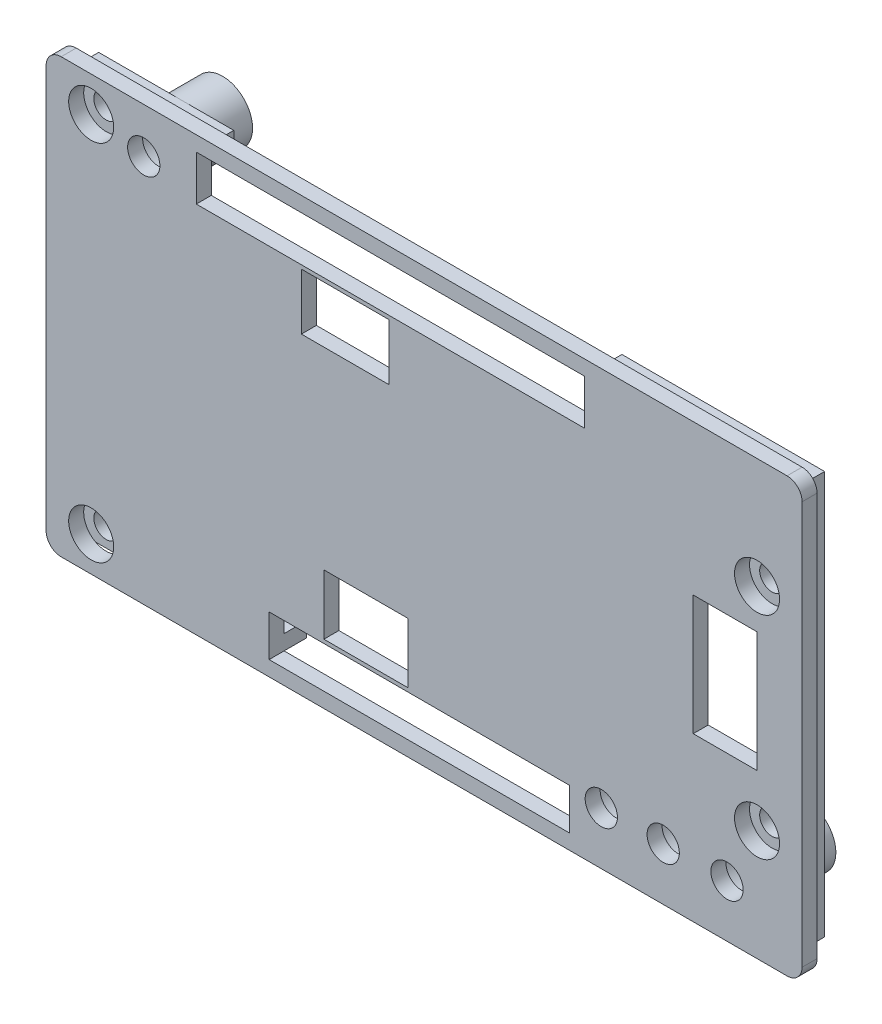
SolidWorks part; units mm, degrees
ref_plane "Front Plane" through (0, 0, 0) normal (0, 0, 1) x (1, 0, 0)
ref_plane "Top Plane" through (0, 0, 0) normal (0, 1, 0) x (1, 0, 0)
ref_plane "Right Plane" through (0, 0, 0) normal (1, 0, 0) x (0, 0, -1)
sketch "Sketch1" plane through (0, 0, 0) normal (0, 0, 1) x (1, 0, 0)
  line L1 (-48.35, 26.85) -> (48.35, 26.85)
  line L2 (-48.35, 26.85) -> (-48.35, -26.85)
  line L3 (-48.35, -26.85) -> (48.35, -26.85)
  line L4 (48.35, 26.85) -> (48.35, -26.85)
  line L5 (-46.35, 24.85) -> (46.35, 24.85)
  line L6 (-46.35, 24.85) -> (-46.35, -24.85)
  line L7 (-46.35, -24.85) -> (46.35, -24.85)
  line L8 (46.35, 24.85) -> (46.35, -24.85)
  line L9 (-50.35, 28.85) -> (50.35, 28.85)
  line L10 (-50.35, 28.85) -> (-50.35, -28.85)
  line L11 (-50.35, -28.85) -> (50.35, -28.85)
  line L12 (50.35, 28.85) -> (50.35, -28.85)
  dimension "D1" = 96.7
  dimension "D2" = 53.7
  dimension "D3" = 26.85
  dimension "D4" = 48.35
  dimension "D5" = 2
  dimension "D6" = 2
  dimension "D7" = 2
  dimension "D8" = 2
  dimension "D9" = 2
  dimension "D10" = 2
  dimension "D11" = 2
  dimension "D12" = 2
extrude "Boss-Extrude1" add sketch "Sketch1" along normal blind 2 contours L8 L5 L6 L7 | L4 L1 L2 L3 L5 L8 L7 L6 | L12 L9 L10 L11 L1 L4 L3 L2 region at (0, 25.7439, 0) region at (0, 0, 0) region at (0, 27.6894, 0)
fillet "Fillet1" radius 2 4 edges at (-50.35, -28.85, 1) (-50.35, 28.85, 1) (50.35, -28.85, 1) (50.35, 28.85, 1)
extrude "Boss-Extrude2" add sketch "Sketch1<3>" against normal blind 3 contours L4 L1 L2 L3 L5 L8 L7 L6 region at (0, 25.7439, 0)
sketch "Sketch1<3>" plane through (0, 0, 0) normal (0, 0, 1) x (1, 0, 0) same geometry as "Sketch1"
sketch "Sketch2" plane through (-48.35, 0, 0) normal (-1, 0, 0) x (0, 0, 1)
  line L4 (-3, -10.005) -> (-3, -20.478)
  line L7 (-3, 26.85) -> (-3, -26.85) construction
  arc A0 (-3, -20.478) -> (-3, -10.005) centre (-5.0085, -15.2415) ccw
  dimension "D4" = 0
extrude "Cut-Extrude2" cut sketch "Sketch2" against normal blind 17 and the other way blind 3
sketch "Sketch4" plane through (0, 0, 0) normal (0, 0, -1) x (-1, 0, 0)
  line L0 (48.35, 26.85) -> (-48.35, 26.85) construction
  line L1 (-48.35, 26.85) -> (-48.35, -26.85) construction
  line L2 (48.35, -26.85) -> (-48.35, -26.85) construction
  line L3 (-48.35, 26.85) -> (-48.35, -26.85) construction
  line L4 (48.35, -17.7654) -> (48.35, -26.85) construction
  line L5 (48.35, -26.85) -> (-48.35, -26.85) construction
  line L7 (48.35, 26.85) -> (48.35, -12.7176) construction
  line L8 (48.35, 26.85) -> (-48.35, 26.85) construction
  circle A2 centre (-44.35, -14.1) radius 1.65
  circle A3 centre (-44.35, 14.1) radius 1.65
  circle A4 centre (44.35, 24.2) radius 1.65
  circle A7 centre (44.35, -24.2) radius 1.65
  dimension "D2" = 4
  dimension "D4" = 4
  dimension "D5" = 3.3
  dimension "D6" = 3.3
  dimension "D10" = 2.65
  dimension "D11" = 3.3
  dimension "D14" = 2.65
  dimension "D15" = 3.3
  dimension "D1" = 12.75
  dimension "D3" = 12.75
  dimension "D9" = 4
  dimension "D13" = 4
sketch "Sketch5" plane through (0, 0, 2) normal (0, 0, 1) x (1, 0, 0)
  line L0 (-48.35, -28.85) -> (48.35, -28.85) construction
  line L1 (-48.35, 26.85) -> (48.35, 26.85)
  line L2 (-48.35, 26.85) -> (-48.35, -26.85)
  line L3 (-48.35, -26.85) -> (48.35, -26.85)
  line L4 (48.35, 26.85) -> (48.35, -26.85)
  line L5 (-50.35, 26.85) -> (-50.35, -26.85) construction
  line L6 (-48.35, 28.85) -> (48.35, 28.85) construction
  line L7 (50.35, 26.85) -> (50.35, -26.85) construction
  line L9 (-20.65, -21.35) -> (19.35, -21.35)
  line L10 (-20.65, -21.35) -> (-20.65, -26.85)
  line L11 (-20.65, -26.85) -> (19.35, -26.85)
  line L12 (19.35, -21.35) -> (19.35, -26.85)
  line L13 (-30.35, 26.85) -> (21.35, 26.85)
  line L14 (-30.35, 26.85) -> (-30.35, 20.85)
  line L15 (-30.35, 20.85) -> (21.35, 20.85)
  line L16 (21.35, 26.85) -> (21.35, 20.85)
  line L17 (35.85, 8.85) -> (44.35, 8.85)
  line L18 (35.85, 8.85) -> (35.85, -7.15)
  line L19 (35.85, -7.15) -> (44.35, -7.15)
  line L20 (44.35, 8.85) -> (44.35, -7.15)
  line L21 (-13.35, -12.85) -> (-2.15, -12.85)
  line L22 (-13.35, -12.85) -> (-13.35, -20.85)
  line L23 (-13.35, -20.85) -> (-2.15, -20.85)
  line L24 (-2.15, -12.85) -> (-2.15, -20.85)
  line L25 (-16.35, 20.35) -> (-4.65, 20.35)
  line L26 (-16.35, 20.35) -> (-16.35, 12.85)
  line L27 (-16.35, 12.85) -> (-4.65, 12.85)
  line L28 (-4.65, 20.35) -> (-4.65, 12.85)
  dimension "D1" = 2
  dimension "D2" = 2
  dimension "D3" = 2
  dimension "D4" = 2
  dimension "D5" = 5.5
  dimension "D6" = 40
  dimension "D7" = 29
  dimension "D8" = 12.5
  dimension "D9" = 4
  dimension "D10" = 16
  dimension "D11" = 18
  dimension "D12" = 6
  dimension "D13" = 18
  dimension "D14" = 27
  dimension "D15" = 32
  dimension "D16" = 53
  dimension "D17" = 6.5
  dimension "D18" = 14
  dimension "D19" = 14
  dimension "D20" = 6
  dimension "D21" = 35
  dimension "D22" = 50.5
extrude "Cut-Extrude4" cut sketch "Sketch5" against normal blind 12.4 contours L16 L1 L14 L15 | L28 L25 L26 L27 | L24 L21 L22 L23 | L12 L9 L10 L3 | L20 L17 L18 L19 region at (-4.5, 23.85, 2) region at (-0.65, -24.1, 2) region at (40.1, 0.85, 2) region at (-7.75, -16.85, 2) region at (-10.5, 16.6, 2)
sketch "Sketch6" plane through (0, 0, 2) normal (0, 0, 1) x (1, 0, 0)
  text T0 "HORMIGA 877\r\nDSI" font "Franklin Gothic Book" height in points 20
extrude "Cut-Extrude5" cut sketch "Sketch6" against normal blind 1
sketch "Sketch7" plane through (0, 0, 2) normal (0, 0, 1) x (1, 0, 0)
  line L0 (-48.35, -28.85) -> (48.35, -28.85) construction
  line L3 (-48.35, -26.85) -> (48.35, -26.85)
  line L4 (48.35, 26.85) -> (48.35, -26.85)
  line L7 (50.35, 26.85) -> (50.35, -26.85) construction
  circle A0 centre (40.35, -21.85) radius 2.15
  circle A1 centre (31.85, -21.85) radius 2.15
  circle A2 centre (23.6, -21.85) radius 2.15
  circle A3 centre (-37.35, 22.85) radius 2.15
  dimension "D5" = 4.3
  dimension "D6" = 4.3
  dimension "D7" = 4.3
  dimension "D14" = 4.3
  dimension "D1" = 2
  dimension "D4" = 2
  dimension "D8" = 5
  dimension "D9" = 5
  dimension "D10" = 5
  dimension "D11" = 8
  dimension "D12" = 16.5
  dimension "D13" = 24.75
extrude "Cut-Extrude6" cut sketch "Sketch7" against normal blind 11 contours A0 | A1 | A2 | A3 region at (40.35, -21.85, 2) region at (31.85, -21.85, 2) region at (23.6, -21.85, 2) region at (-37.35, 22.85, 2)
sketch "Sketch8" plane through (0, 0, 0) normal (0, 0, -1) x (-1, 0, 0)
  circle A0 centre (37.35, 22.85) radius 3.5
  arc A1 (36.561, 24.85) -> (38.139, 24.85) centre (37.35, 22.85) ccw construction
  circle A2 centre (-40.35, -21.85) radius 3.5
  circle A3 centre (-31.85, -21.85) radius 3.5
  circle A4 centre (-23.6, -21.85) radius 3.5
  circle A5 centre (-40.35, -21.85) radius 2.15 construction
  circle A6 centre (-31.85, -21.85) radius 2.15 construction
  circle A7 centre (-23.6, -21.85) radius 2.15 construction
  dimension "D1" = 7
  dimension "D2" = 7
  dimension "D3" = 7
  dimension "D4" = 7
extrude "Cut-Extrude7" cut sketch "Sketch8" along normal blind 11
sketch "Sketch9" plane through (0, 0, 0) normal (0, 0, -1) x (-1, 0, 0)
  circle A0 centre (37.35, 22.85) radius 4
  circle A1 centre (37.35, 22.85) radius 3.5
  circle A2 centre (-23.6, -21.85) radius 4
  circle A3 centre (-23.6, -21.85) radius 3.5
  circle A4 centre (-31.85, -21.85) radius 3.5
  circle A5 centre (-31.85, -21.85) radius 4
  circle A6 centre (-40.35, -21.85) radius 3.5
  circle A7 centre (-40.35, -21.85) radius 4
  arc A9 (-25.4028, -24.85) -> (-21.7972, -24.85) centre (-23.6, -21.85) ccw construction
  arc A10 (-42.1528, -24.85) -> (-38.5472, -24.85) centre (-40.35, -21.85) ccw construction
  arc A11 (-33.6528, -24.85) -> (-30.0472, -24.85) centre (-31.85, -21.85) ccw construction
  arc A13 (40.2223, 24.85) -> (34.4777, 24.85) centre (37.35, 22.85) ccw construction
  dimension "D1" = 8
  dimension "D2" = 8
  dimension "D3" = 8
  dimension "D4" = 8
extrude "Boss-Extrude4" add sketch "Sketch9" along normal blind 8.5
extrude "Cut-Extrude8" cut sketch "Sketch4" against normal blind 10 and the other way blind 10
sketch "Sketch11" plane through (0, 0, 0) normal (0, 0, -1) x (-1, 0, 0)
  line L0 (-48.35, 26.85) -> (-48.35, -26.85) construction
  line L1 (-48.35, 18.1) -> (-40.35, 18.1)
  line L2 (-48.35, 18.1) -> (-48.35, 10.1)
  line L3 (-48.35, 10.1) -> (-40.35, 10.1)
  line L4 (-40.35, 18.1) -> (-40.35, 10.1)
  line L5 (41.15, 26.85) -> (48.35, 26.85)
  line L6 (41.15, 26.85) -> (41.15, 20.85)
  line L7 (41.15, 20.85) -> (48.35, 20.85)
  line L8 (48.35, 26.85) -> (48.35, 20.85)
  line L9 (41.35, -20.85) -> (48.35, -20.85)
  line L10 (41.35, -20.85) -> (41.35, -26.85)
  line L11 (41.35, -26.85) -> (48.35, -26.85)
  line L12 (48.35, -20.85) -> (48.35, -26.85)
  line L13 (-48.35, -10.1) -> (-40.35, -10.1)
  line L14 (-48.35, -10.1) -> (-48.35, -18.1)
  line L15 (-48.35, -18.1) -> (-40.35, -18.1)
  line L16 (-40.35, -10.1) -> (-40.35, -18.1)
  line L17 (48.35, -17.7654) -> (48.35, -26.85) construction
  line L18 (48.35, -26.85) -> (20.65, -26.85) construction
  line L19 (48.35, 26.85) -> (30.35, 26.85) construction
  line L20 (48.35, 26.85) -> (48.35, -12.7176) construction
  circle A0 centre (-44.35, 14.1) radius 1.65 construction
  circle A1 centre (-44.35, 14.1) radius 1.65
  circle A2 centre (-44.35, -14.1) radius 1.65 construction
  circle A3 centre (-44.35, -14.1) radius 1.65
  circle A4 centre (44.35, -24.2) radius 1.65
  arc A5 (45.8666, -24.85) -> (42.8334, -24.85) centre (44.35, -24.2) ccw construction
  circle A6 centre (44.35, 24.2) radius 1.65
  arc A7 (42.8334, 24.85) -> (45.8666, 24.85) centre (44.35, 24.2) ccw construction
  dimension "D2" = 4
  dimension "D1" = 8
  dimension "D3" = 4
  dimension "D4" = 8
  dimension "D5" = 8
  dimension "D6" = 8
  dimension "D7" = 4
  dimension "D8" = 7
  dimension "D9" = 6
  dimension "D10" = 7.2
  dimension "D11" = 6
extrude "Boss-Extrude9" add sketch "Sketch11" along normal blind 3
fillet "Fillet2" radius 2 14 edges at (-41.35, -22.85, 0) (-41.15, 21.2255, 0) (-46.35, 20.85, -1.5) (-43.75, 20.85, 0) (-41.35, -24.85, -1.5) (-43.85, -20.85, 0) (-41.35, -20.85, -1.5) (40.35, -10.1, -1.5) (43.35, -10.1, 0) (40.35, -13.975, 0) (46.35, 18.1, -1.5) (40.35, 18.1, -1.5) (43.35, 18.1, 0) (40.35, 14.1, 0)
sketch "Sketch12" plane through (0, 0, 2) normal (0, 0, 1) x (1, 0, 0)
  circle A0 centre (-44.35, 24.2) radius 3
  circle A1 centre (-44.35, -24.2) radius 3
  circle A2 centre (44.35, -14.1) radius 3
  circle A3 centre (44.35, 14.1) radius 3
  circle A4 centre (44.35, 14.1) radius 1.65 construction
  circle A5 centre (44.35, -14.1) radius 1.65 construction
  circle A6 centre (-44.35, -24.2) radius 1.65 construction
  circle A7 centre (-44.35, 24.2) radius 1.65 construction
  dimension "D1" = 6
extrude "Cut-Extrude9" cut sketch "Sketch12" against normal blind 2
sketch "Sketch13" plane through (0, 0, 2) normal (0, 0, 1) x (1, 0, 0)
  line L1 (-32.0099, 7.5125) -> (20.5778, 7.5125)
  line L2 (-32.0099, 7.5125) -> (-32.0099, -12.0854)
  line L3 (-32.0099, -12.0854) -> (20.5778, -12.0854)
  line L4 (20.5778, 7.5125) -> (20.5778, -12.0854)
extrude "Boss-Extrude10" add sketch "Sketch13" against normal blind 2
